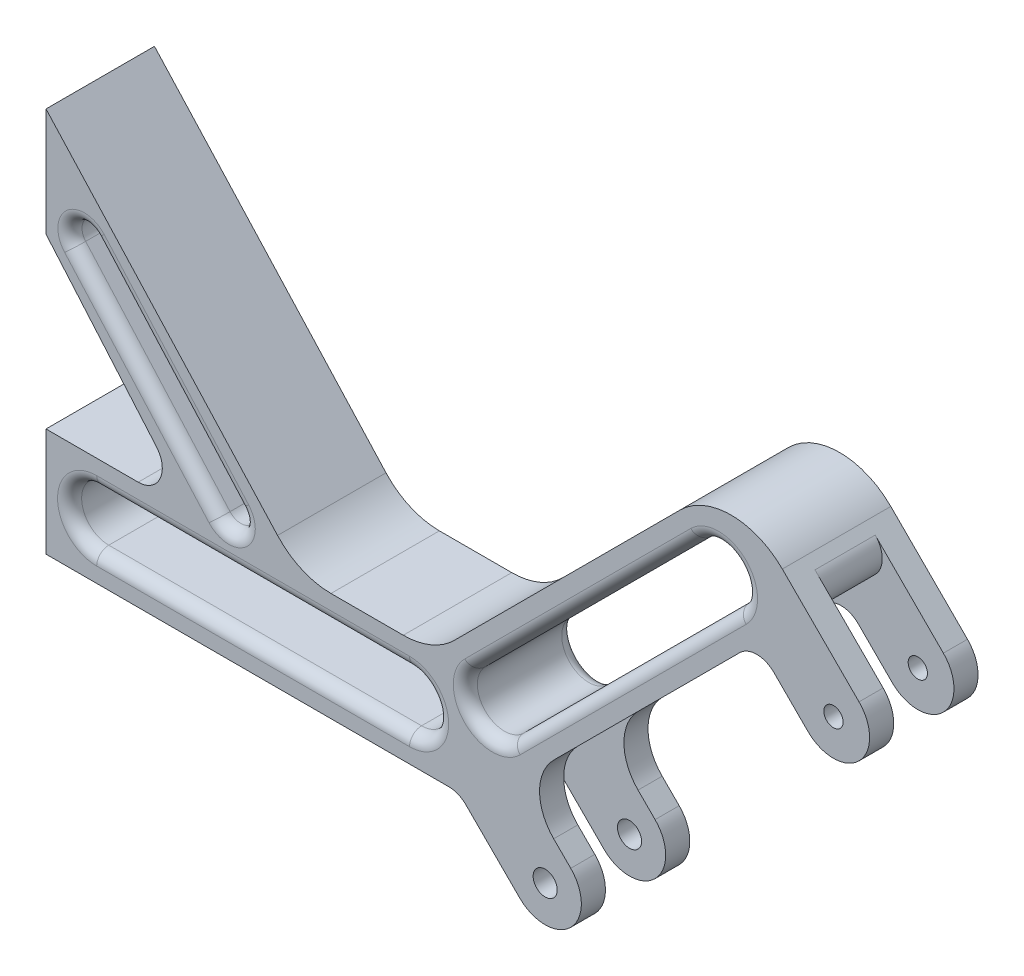
SolidWorks part; units mm, degrees
material "6061 Alloy"
ref_plane "Front Plane" through (0, 0, 0) normal (0, 0, 1) x (1, 0, 0)
ref_plane "Top Plane" through (0, 0, 0) normal (0, 1, 0) x (1, 0, 0)
ref_plane "Right Plane" through (0, 0, 0) normal (1, 0, 0) x (0, 0, -1)
sketch "Sketch1" plane through (0, 0, 0) normal (1, 0, 0) x (0, 0, -1)
  line L1 (-20, 20) -> (20, 20)
  line L2 (-20, 20) -> (-20, -20)
  line L3 (-20, -20) -> (20, -20)
  line L4 (20, 20) -> (20, -20) construction
  line L5 (-20, 20) -> (20, -20) construction
  line L6 (-20, -20) -> (20, 20) construction
  line L7 (-22.5, 22.5) -> (22.5, 22.5)
  line L8 (-22.5, 22.5) -> (-22.5, -22.5)
  line L9 (-22.5, -22.5) -> (22.5, -22.5)
  line L10 (22.5, 22.5) -> (22.5, -22.5)
  line L11 (-22.5, 22.5) -> (22.5, -22.5) construction
  line L12 (-22.5, -22.5) -> (22.5, 22.5) construction
  point P0 (0, 0)
  point P6 (0, 0)
  dimension "D1" = 40
  dimension "D2" = 40
  dimension "D3" = 45
  dimension "D4" = 45
sketch "Sketch2" plane through (0, 0, 0) normal (0, 0, 1) x (1, 0, 0)
  line L0 (0, 0) -> (170, 0)
  line L1 (300.2297, 0) -> (300.2297, 130.2297) construction
  line L2 (300.2297, 35.5495) -> (173.2297, 35.5495) construction
  line L3 (300.2297, 130.2297) -> (170, 0)
  line L4 (170, 0) -> (300.2297, 0) construction
  line L5 (300.2297, 130.2297) -> (347.9594, 82.5)
  line L6 (347.9594, 82.5) -> (326.7462, 61.2868)
  line L7 (326.7462, 61.2868) -> (279.0165, 109.0165)
  line L8 (337.3528, 71.8934) -> (324.9741, 84.2721) construction
  line L9 (326.7462, 82.5) -> (326.7462, 0) construction
  line L10 (300.2297, 0) -> (326.7462, 0)
  line L11 (82.5, 22.5) -> (82.5, 37.8458) construction
  line L12 (0, 22.5) -> (92.0876, 22.5)
  line L13 (0, 22.5) -> (0, -22.5) construction
  line L14 (0, 22.5) -> (0, -22.5) construction
  line L15 (82.5, 22.5) -> (0, 105)
  line L16 (0, 22.5) -> (0, 105) construction
  arc A0 (34.4369, 70.5631) -> (25.2297, 0) centre (300.2297, 0) ccw construction
  circle A1 centre (326.7462, 82.5) radius 5.9071
  dimension "D2" = 550
  dimension "D7" = 15
  dimension "D4" = 82.5
  dimension "D1" = 170
  dimension "D3" = 135
  dimension "D5" = 30
  dimension "D6" = 67.5
  dimension "D8" = 82.5
  dimension "D9" = 45
sweep "Sweep1" add profiles "Sketch1" path "Sketch2"
sketch "Sketch5" plane through (0, 0, 22.5) normal (0, 0, 1) x (1, 0, 0)
  line L0 (170, 0) -> (217.7297, -47.7297) construction
  line L1 (179.3198, -22.5) -> (160.6802, 22.5) construction
  line L2 (179.3198, -22.5) -> (0, -22.5) construction
  line L3 (207.1231, -58.3363) -> (159.3934, -10.6066)
  line L4 (159.3934, -10.6066) -> (180.6066, 10.6066)
  line L5 (207.1231, -58.3363) -> (228.3363, -37.1231)
  line L6 (228.3363, -37.1231) -> (180.6066, 10.6066)
  line L7 (170, 0) -> (0, 0) construction
  line L8 (170, 0) -> (279.0165, 109.0165) construction
  line L9 (284.3198, 146.1396) -> (316.1396, 114.3198) construction
  line L10 (300.2297, 130.2297) -> (347.9594, 82.5)
  line L11 (347.9594, 82.5) -> (326.7462, 61.2868)
  line L12 (326.7462, 61.2868) -> (279.0165, 109.0165)
  line L13 (337.3528, 71.8934) -> (318.0612, 91.185) construction
  line L14 (300.2297, 130.2297) -> (279.0165, 109.0165)
  circle A0 centre (207.1231, -37.1231) radius 5
  circle A1 centre (326.7462, 82.5) radius 4
  point P9 (217.7297, -47.7297)
  point P14 (170, 0)
  dimension "D4" = 10
  dimension "D5" = 15
  dimension "D8" = 8
  dimension "D9" = 15
  dimension "D1" = 135
  dimension "D2" = 67.5
  dimension "D3" = 30
  dimension "D6" = 67.5
  dimension "D7" = 30
  dimension "D10" = 154.1726
extrude "Boss-Extrude2" add sketch "Sketch5" against normal blind 10
fillet "Fillet2" radius 15 4 edges at (207.1231, -58.3363, 17.5) (228.3363, -37.1231, 17.5) (326.7462, 61.2868, 17.5) (347.9594, 82.5, 17.5)
mirror "Mirror1" about plane through (0, 0, 0) normal (0, 0, 1) of "Boss-Extrude2", "Fillet2"
sketch "Sketch6" plane through (0, 22.5, 0) normal (0, 1, 0) x (1, 0, 0)
  line L0 (0, 0) -> (170, 0) construction
  line L1 (60, 22.5) -> (105, 22.5)
  line L2 (60, 22.5) -> (60, -22.5)
  line L3 (60, -22.5) -> (105, -22.5)
  line L4 (105, 22.5) -> (105, -22.5)
  line L5 (60, 22.5) -> (105, -22.5) construction
  line L6 (60, -22.5) -> (105, 22.5) construction
  line L7 (160.6802, -22.5) -> (0, -22.5) construction
  line L8 (0, 22.5) -> (0, -22.5) construction
  point P0 (82.5, 0)
  dimension "D1" = 60
sketch "Sketch7" plane through (0, 0, 0) normal (-1, 0, 0) x (0, 0, 1)
  line L0 (0, 130.2297) -> (0, 82.5) construction
  line L1 (-22.5, 137.5) -> (22.5, 137.5)
  line L2 (-22.5, 137.5) -> (-22.5, 92.5)
  line L3 (-22.5, 92.5) -> (22.5, 92.5)
  line L4 (22.5, 137.5) -> (22.5, 92.5)
  line L5 (-22.5, 137.5) -> (22.5, 92.5) construction
  line L6 (-22.5, 92.5) -> (22.5, 137.5) construction
  line L7 (22.5, 22.5) -> (-22.5, 22.5) construction
  point P0 (0, 115)
  dimension "D1" = 45
  dimension "D2" = 70
loft "Loft1" add profiles "Sketch6", "Sketch7" connector at (105, 22.5, -22.5) connector at (0, 137.5, -22.5)
fillet "Fillet3" radius 10 5 edges at (294.9264, 93.1066, 17.5) (294.9264, 93.1066, -17.5) (171.2868, -22.5, -17.5) (171.2868, -22.5, 17.5) tangent propagation no
fillet "Fillet4" radius 30 1 edges at (284.3198, 146.1396, 0)
fillet "Fillet5" radius 30 1 edges
sketch "Sketch8" plane through (0, 0, 22.5) normal (0, 0, 1) x (1, 0, 0)
  line L0 (21.0386, 0) -> (150.8392, 0) construction
  line L1 (0, 0) -> (170, 0) construction
  line L2 (21.0386, 11.25) -> (150.8392, 11.25)
  line L3 (21.0386, -11.25) -> (150.8392, -11.25)
  line L4 (185.2441, 15.2441) -> (279.0165, 109.0165) construction
  line L5 (300.2297, 130.2297) -> (170, 0) construction
  line L6 (177.2891, 23.1991) -> (271.0616, 116.9715)
  line L7 (193.1991, 7.2891) -> (286.9715, 101.0616)
  line L8 (0, 115) -> (82.5, 22.5) construction
  line L9 (0, 92.5) -> (0, 137.5) construction
  line L10 (15.9385, 97.1295) -> (82.5, 22.5) construction
  line L11 (20.4163, 101.1232) -> (86.9778, 26.4937)
  line L12 (11.4607, 93.1359) -> (78.0222, 18.5063)
  line L13 (82.5, 22.5) -> (75.8439, 29.963)
  arc A0 (21.0386, 11.25) -> (21.0386, -11.25) centre (21.0386, 0) ccw
  arc A1 (150.8392, -11.25) -> (150.8392, 11.25) centre (150.8392, 0) ccw
  arc A2 (177.2891, 23.1991) -> (193.1991, 7.2891) centre (185.2441, 15.2441) ccw
  arc A3 (286.9715, 101.0616) -> (271.0616, 116.9715) centre (279.0165, 109.0165) ccw
  arc A4 (20.4163, 101.1232) -> (11.4607, 93.1359) centre (15.9385, 97.1295) ccw
  arc A5 (78.0222, 18.5063) -> (86.9778, 26.4937) centre (82.5, 22.5) ccw
  arc A6 (71.3661, 25.9693) -> (80.3216, 33.9566) centre (75.8439, 29.963) ccw
  point P4 (85.9389, 0)
  point P9 (232.1303, 62.1303)
  point P25 (49.2193, 59.8148)
  dimension "D1" = 11.25
  dimension "D2" = 11.25
  dimension "D3" = 6
  dimension "D4" = 100
  dimension "D5" = 10
extrude "Cut-Extrude1" cut sketch "Sketch8" against normal through all contours L7 A3 L6 A2 | L12 A6 L11 A4 | L3 A1 L2 A0 region at (232.1303, 62.1303, 22.5) region at (45.8912, 63.5462, 22.5)
fillet "Fillet6" radius 5 20 edges at (41.4134, 59.5526, 22.5) (11.9448, 101.6073, 22.5) (50.369, 67.5399, 22.5) (240.0853, 54.1754, 22.5) (177.2891, 7.2891, 22.5) (224.1754, 70.0853, 22.5) (162.0892, 0, 22.5) (85.9389, -11.25, 22.5) (9.7886, 0, 22.5) (9.7886, 0, -22.5) (85.9389, 11.25, -22.5) (162.0892, 0, -22.5) (177.2891, 7.2891, -22.5) (224.1754, 70.0853, -22.5) (286.9715, 116.9715, -22.5) (286.9715, 116.9715, 22.5) (85.9389, 11.25, 22.5) (85.9389, -11.25, -22.5) (240.0853, 54.1754, -22.5) (79.8375, 25.4852, 22.5)
fillet "Fillet7" radius 20 2 edges at (196.5165, -5.3033, 17.5) (196.5165, -5.3033, -17.5)
fillet "Fillet8" radius 25 1 edges at (179.3198, -22.5, 0)
fillet "Fillet10" radius 5 4 edges at (11.9448, 101.6073, -22.5) (41.4134, 59.5526, -22.5) (79.8375, 25.4852, -22.5) (50.369, 67.5399, -22.5)
fillet "Fillet11" radius 10 1 edges at (316.1396, 114.3198, 0)
fillet "Fillet12" radius 30 1 edges at (160.6802, 22.5, 0)
